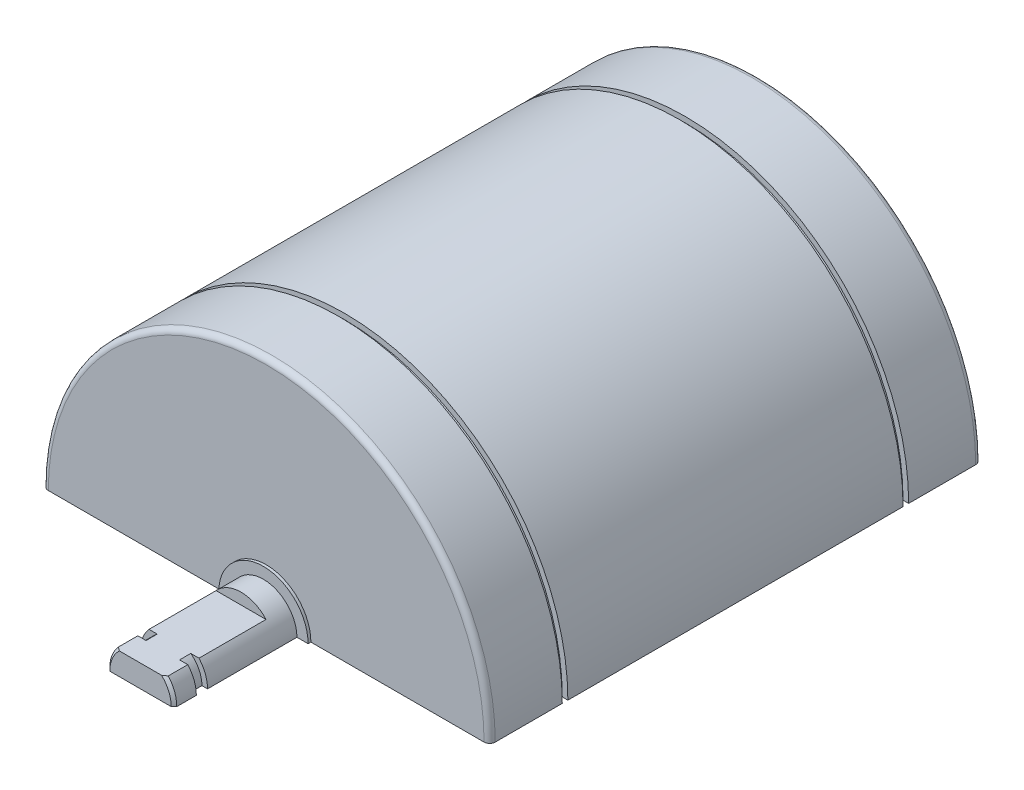
SolidWorks part; units mm, degrees
ref_plane "Plan de face" through (0, 0, 0) normal (0, 0, 1) x (1, 0, 0)
ref_plane "Plan de dessus" through (0, 0, 0) normal (0, 1, 0) x (1, 0, 0)
ref_plane "Plan de droite" through (0, 0, 0) normal (1, 0, 0) x (0, 0, -1)
sketch "Esquisse1" plane through (0, 0, 0) normal (0, 1, 0) x (1, 0, 0)
  line L0 (0, 0) -> (0, 72.5853) construction
  line L1 (0, 0) -> (3, 0) construction
  line L2 (20, 0) -> (4, 0)
  line L3 (20, 44) -> (20, 37.5)
  line L4 (20, 37.5) -> (19.5, 37.5)
  line L5 (19.5, 37.5) -> (19.5, 37)
  line L6 (19.5, 37) -> (20, 37)
  line L7 (20, 37) -> (20, 7)
  line L8 (20, 7) -> (19.5, 7)
  line L9 (19.5, 7) -> (19.5, 6.5)
  line L10 (19.5, 6.5) -> (20, 6.5)
  line L11 (20, 6.5) -> (20, 0)
  line L12 (3, -0.25) -> (3, -8.25)
  line L13 (3, -11.25) -> (0, -11.25)
  line L14 (8.5, 44.25) -> (8.5, 49)
  line L15 (8.5, 49) -> (0, 49)
  line L16 (10, 44) -> (20, 44)
  line L17 (0, -11.25) -> (0, 49)
  line L18 (8.5, 44.25) -> (10, 44.25)
  line L19 (10, 44.25) -> (10, 44)
  line L20 (3, -0.25) -> (4, -0.25)
  line L21 (4, -0.25) -> (4, 0)
  line L22 (4, 0) -> (36.365, 0) construction
  line L23 (3, -9.25) -> (2.5, -9.25)
  line L24 (2.5, -9.25) -> (2.5, -8.25)
  line L25 (2.5, -8.25) -> (3, -8.25)
  line L26 (3, -9.25) -> (3, -11.25)
  dimension "D2" = 20
  dimension "D3" = 0.5
  dimension "D4" = 0.5
  dimension "D5" = 0.5
  dimension "D6" = 0.5
  dimension "D7" = 0.5
  dimension "D8" = 0.5
  dimension "D9" = 6.5
  dimension "D10" = 30
  dimension "D11" = 8.5
  dimension "D12" = 3
  dimension "D13" = 44
  dimension "D14" = 11.25
  dimension "D15" = 5
  dimension "D16" = 0.25
  dimension "D17" = 10
  dimension "D18" = 0.25
  dimension "D19" = 4
  dimension "D20" = 2
  dimension "D21" = 1
  dimension "D22" = 0.5
revolve "Révolution1" add sketch "Esquisse1" angle 360 about L0
sketch "Esquisse3" plane through (0, 0, 11.25) normal (0, 0, 1) x (1, 0, 0)
  line L0 (-2.2361, 2) -> (2.2361, 2)
  circle A1 centre (0, 0) radius 3
  arc A2 (2.2361, 2) -> (-2.2361, 2) centre (0, 0) ccw
  dimension "D2" = 2
  dimension "D1" = 0
extrude "Enlèv. mat.-Extru.2" cut sketch "Esquisse3" against normal blind 9
chamfer "Chanfrein1" distance 0.25 angle 45 1 edges at (0, -3, 11.25)
fillet "Congé1" radius 0.5 2 edges at (20, 0, -44) (20, 0, 0)
ref_plane "Plan1" through (0, -29, 0) normal (0, 1, 0) x (-1, 0, 0)
sketch "Esquisse4" plane through (0, -29, 0) normal (0, 1, 0) x (-1, 0, 0)
  line L0 (0, 0) -> (0, -49.3887) construction
  line L1 (-20, -22) -> (27.9191, -22) construction
  line L2 (-20, -7) -> (-20, -37) construction
  circle A0 centre (0, -22) radius 10
  dimension "D1" = 20
extrude "Enlèv. mat.-Extru.3" cut sketch "Esquisse4" along normal blind 23
fillet "Congé2" radius 1 1 edges at (1.0091, -19.9745, -12.051)
sketch "Esquisse5" plane through (0, 0, 0) normal (1, 0, 0) x (0, 0, -1)
  line L1 (-17.1498, 0) -> (58.2557, 0)
  line L2 (-17.1498, 0) -> (-17.1498, -27.4535)
  line L3 (-17.1498, -27.4535) -> (58.2557, -27.4535)
  line L4 (58.2557, 0) -> (58.2557, -27.4535)
extrude "Enlèv. mat.-Extru.4" cut sketch "Esquisse5" against normal mid plane 60
shell "Coque1" thickness 1 removed face at (0, 0, -15.51)
sketch "Esquisse6" plane through (0, 0, -48) normal (0, 0, 1) x (1, 0, 0)
  line L1 (-7.5, 0) -> (7.5, 0)
  line L2 (-7.5, 0) -> (7.5, 0)
  arc A1 (7.5, 0) -> (-7.5, 0) centre (0, 0) ccw
  arc A2 (7.5, 0) -> (-7.5, 0) centre (0, 0) ccw
  dimension "D1" = 0
extrude "Enlèv. mat.-Extru.5" cut sketch "Esquisse6" against normal blind 10
sketch "Esquisse7" plane through (0, 0, 0) normal (0, 1, 0) x (1, 0, 0)
  line L1 (0, 0) -> (0, 71.8652) construction
  line L2 (8.5, 49) -> (-8.5, 49) construction
  circle A0 centre (1.5, 46.5) radius 2.5
  dimension "D1" = 5
  dimension "D2" = 2.5
  dimension "D3" = 1.5
extrude "Boss.-Extru.1" add sketch "Esquisse7" along normal up to surface (7.3485 mm away)
ref_plane "Plan2" through (0, 11, 0) normal (0, -1, 0) x (1, 0, 0)
sketch "Esquisse9" plane through (0, 11, 0) normal (0, -1, 0) x (1, 0, 0)
  circle A0 centre (1.5, -46.5) radius 2.25
  dimension "D1" = 4.5
extrude "Enlèv. mat.-Extru.6" cut sketch "Esquisse9" along normal blind 7
hole_wizard "Dégagement M22" positions "Esquisse3D2" profile "Esquisse10" hole size "M2" standard "ISO" end condition through all
sketch3d "Esquisse3D2"
  line L0 (1.5, 7.3214, -46.5) -> (1.5, 0, -46.5) construction
  point P0 (1.5, 0, -46.5)
sketch "Esquisse10" plane through (1.5, 0, -46.5) normal (1, 0, 0) x (0, 0, -1)
  line L0 (0, 0) -> (0, 20)
  line L1 (0, 20) -> (1.2, 20)
  line L2 (1.2, 20) -> (1.2, 0)
  line L5 (1.2, 0) -> (0, 0)
  line L11 (0, -6.35) -> (0, 107.95) construction
  dimension "Diamètre du perçage jusqu'au prochain" = 2.4
  dimension "Profondeur du perçage jusqu'au prochain" = 20
sketch "Esquisse11" plane through (0, 0, 0) normal (0, -1, 0) x (1, 0, 0)
  circle A0 centre (1.5, -46.5) radius 1.5
  circle A1 centre (1.5, -46.5) radius 2.5 construction
  circle A2 centre (1.5, -46.5) radius 2.5
  dimension "D1" = 3
extrude "Boss.-Extru.2" add sketch "Esquisse11" along normal blind 1
sketch "Esquisse12" plane through (0, 0, 0) normal (0, -1, 0) x (1, 0, 0)
  circle A0 centre (1.5, -46.5) radius 1.2 construction
  circle A1 centre (1.5, -46.5) radius 1.5
  circle A2 centre (1.5, -46.5) radius 1.5
  circle A3 centre (1.5, -46.5) radius 1.2
  dimension "D1" = 0
extrude "Enlèv. mat.-Extru.7" cut sketch "Esquisse12" against normal blind 1
